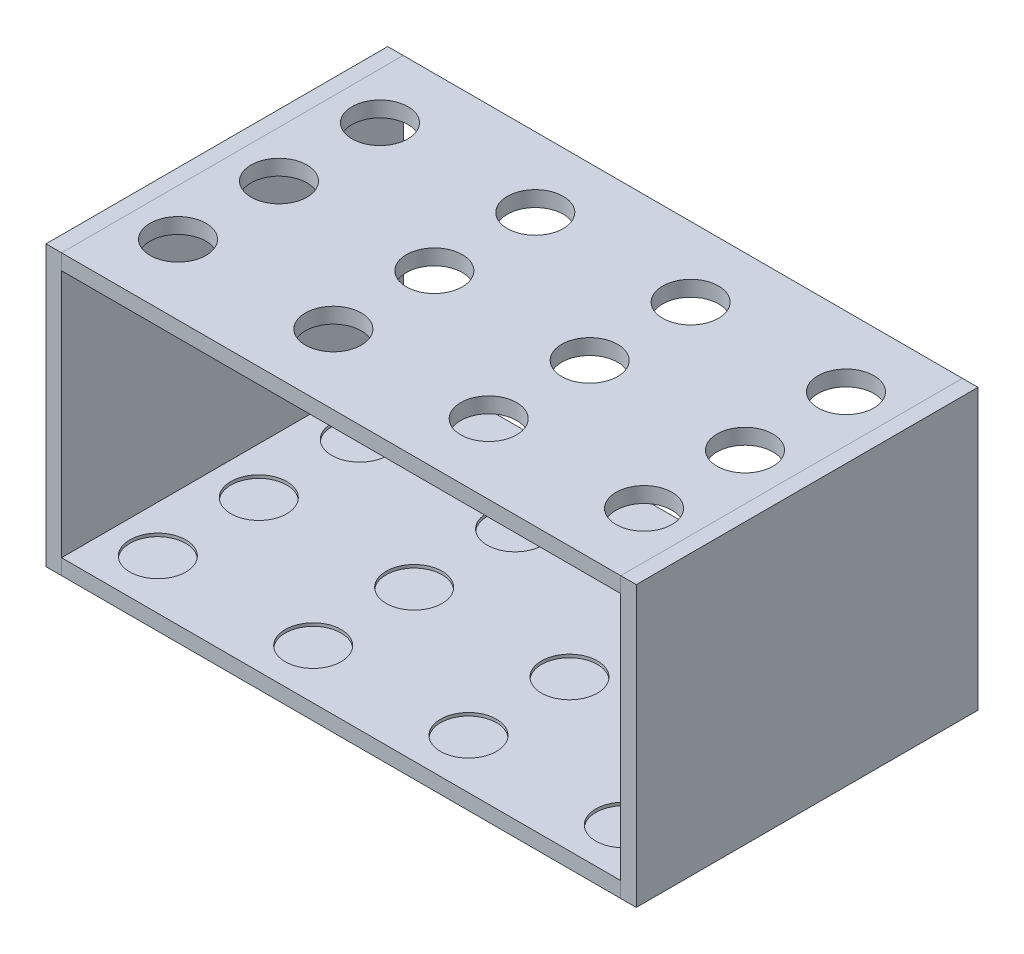
SolidWorks part; units mm, degrees
note: The reader was unsure of these and kept them because the rebuilt part matched: shared geometry of "草圖8<2>", "草圖1<2>".
ref_plane "前基準面" through (0, 0, 0) normal (0, 0, 1) x (1, 0, 0)
ref_plane "上基準面" through (0, 0, 0) normal (0, 1, 0) x (1, 0, 0)
ref_plane "右基準面" through (0, 0, 0) normal (1, 0, 0) x (0, 0, -1)
sketch "草圖1" plane through (0, 0, 0) normal (0, 1, 0) x (1, 0, 0)
  line L0 (0, 0) -> (0, 89.7988) construction
  line L1 (-90, -55) -> (90, -55)
  line L2 (-90, -55) -> (-90, 55)
  line L3 (-90, 55) -> (90, 55)
  line L4 (90, -55) -> (90, 55)
  line L5 (-90, -55) -> (90, 55) construction
  line L6 (-90, 55) -> (90, -55) construction
  point P8 (0, 0)
  point P11 (0, 0)
  point P34 (0, 0)
  point P35 (0, 0)
  point P36 (0, 0)
  dimension "D7" = 180
  dimension "D8" = 110
extrude "填料-伸長1" add sketch "草圖1" along normal blind 5
sketch "草圖2" plane through (0, 0, 0) normal (0, -1, 0) x (1, 0, 0)
  line L0 (0, 70.3147) -> (0, -70.3147) construction
  line L1 (-97.7617, 0) -> (97.7617, 0) construction
  circle A0 centre (-75, 0) radius 9
  circle A1 centre (-75, -32.5) radius 9
  circle A2 centre (-75, 32.5) radius 9
  circle A3 centre (-25, 32.5) radius 9
  circle A4 centre (-25, 0) radius 9
  circle A5 centre (-25, -32.5) radius 9
  circle A6 centre (25, 32.5) radius 9
  circle A7 centre (25, 0) radius 9
  circle A8 centre (25, -32.5) radius 9
  circle A9 centre (75, 32.5) radius 9
  circle A10 centre (75, 0) radius 9
  circle A11 centre (75, -32.5) radius 9
  point P12 (0, 0)
  point P30 (0, 0)
  point P31 (0, 0)
  point P32 (0, 0)
  point P33 (0, 0)
  dimension "D1" = 18
  dimension "D2" = 150
  dimension "D3" = 65
  dimension "D5" = 50
  dimension "D4" = 4
extrude "除料-伸長4" cut sketch "草圖2" against normal through all
sketch "草圖8" plane through (90, 0, 0) normal (1, 0, 0) x (0, 0, -1)
  line L1 (-55, -85) -> (55, -85)
  line L2 (-55, -85) -> (-55, 5)
  line L3 (-55, 5) -> (55, 5)
  line L4 (55, -85) -> (55, 5)
  line L5 (-55, -85) -> (55, 5) construction
  line L6 (-55, 5) -> (55, -85) construction
  point P0 (0, -40)
  point P6 (0, 0)
  point P7 (0, 0)
  point P9 (0, 0)
  dimension "D1" = 90
extrude "填料-伸長2" add sketch "草圖8" along normal blind 5 separate body
extrude "填料-伸長3" add sketch "草圖8<2>" against normal blind 5 from surface at -180 separate body starting at face at (-90, 2.5, 0)
sketch "草圖8<2>" plane through (90, 0, 0) normal (1, 0, 0) x (0, 0, -1) same geometry as "草圖8"
extrude "填料-伸長4" add sketch "草圖1<2>" along normal blind 5 from surface at -85 separate body starting at face at (-92.5, -85, 0)
sketch "草圖1<2>" plane through (0, 0, 0) normal (0, 1, 0) x (1, 0, 0) same geometry as "草圖1"
sketch "草圖11" plane through (0, -80, 6.5) normal (0, -1, 0) x (1, 0, 0)
  line L0 (0, 70.3147) -> (0, -70.3147) construction
  line L1 (-97.7617, 0) -> (97.7617, 0) construction
  line L2 (-90, 48.5) -> (-90, -61.5) construction
  line L3 (90, -61.5) -> (90, 48.5) construction
  line L4 (90, 48.5) -> (-90, 48.5) construction
  circle A0 centre (-75, 0) radius 9
  circle A1 centre (-75, -32.5) radius 9
  circle A2 centre (-75, 32.5) radius 9
  circle A3 centre (-25, 32.5) radius 9
  circle A4 centre (-25, 0) radius 9
  circle A5 centre (-25, -32.5) radius 9
  circle A6 centre (25, 32.5) radius 9
  circle A7 centre (25, 0) radius 9
  circle A8 centre (25, -32.5) radius 9
  circle A9 centre (75, 32.5) radius 9
  circle A10 centre (75, 0) radius 9
  circle A11 centre (75, -32.5) radius 9
  point P12 (0, 0)
  point P30 (0, 0)
  point P31 (0, 0)
  dimension "D1" = 16
extrude "除料-伸長5" cut sketch "草圖11" along normal blind 1
